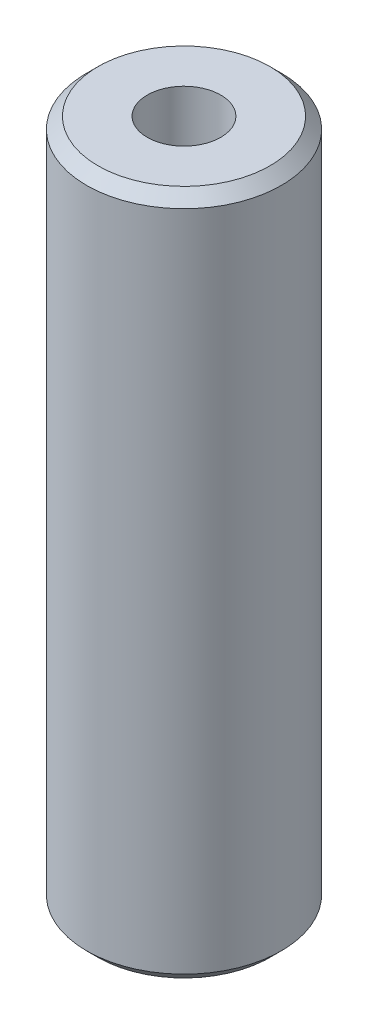
SolidWorks part; units mm, degrees
ref_plane "Front Plane" through (0, 0, 0) normal (0, 0, 1) x (1, 0, 0)
ref_plane "Top Plane" through (0, 0, 0) normal (0, 1, 0) x (1, 0, 0)
ref_plane "Right Plane" through (0, 0, 0) normal (1, 0, 0) x (0, 0, -1)
sketch "Sketch1" plane through (0, 0, 0) normal (0, 1, 0) x (1, 0, 0)
  circle A0 centre (0, 0) radius 12.5
  dimension "SHAFT_OD" = 25
extrude "Boss-Extrude1" add sketch "Sketch1" along normal blind 88.0418
sketch "Sketch2" plane through (0, 0, 0) normal (0, 1, 0) x (1, 0, 0)
  circle A0 centre (0, 0) radius 4.7165
  dimension "BORE_D" = 9.4331
extrude "Cut-Extrude1" cut sketch "Sketch2" along normal through all
chamfer "Chamfer1" distance 1.4561 angle 45 2 edges at (0, 88.0418, 12.5) (0, 0, 12.5)
